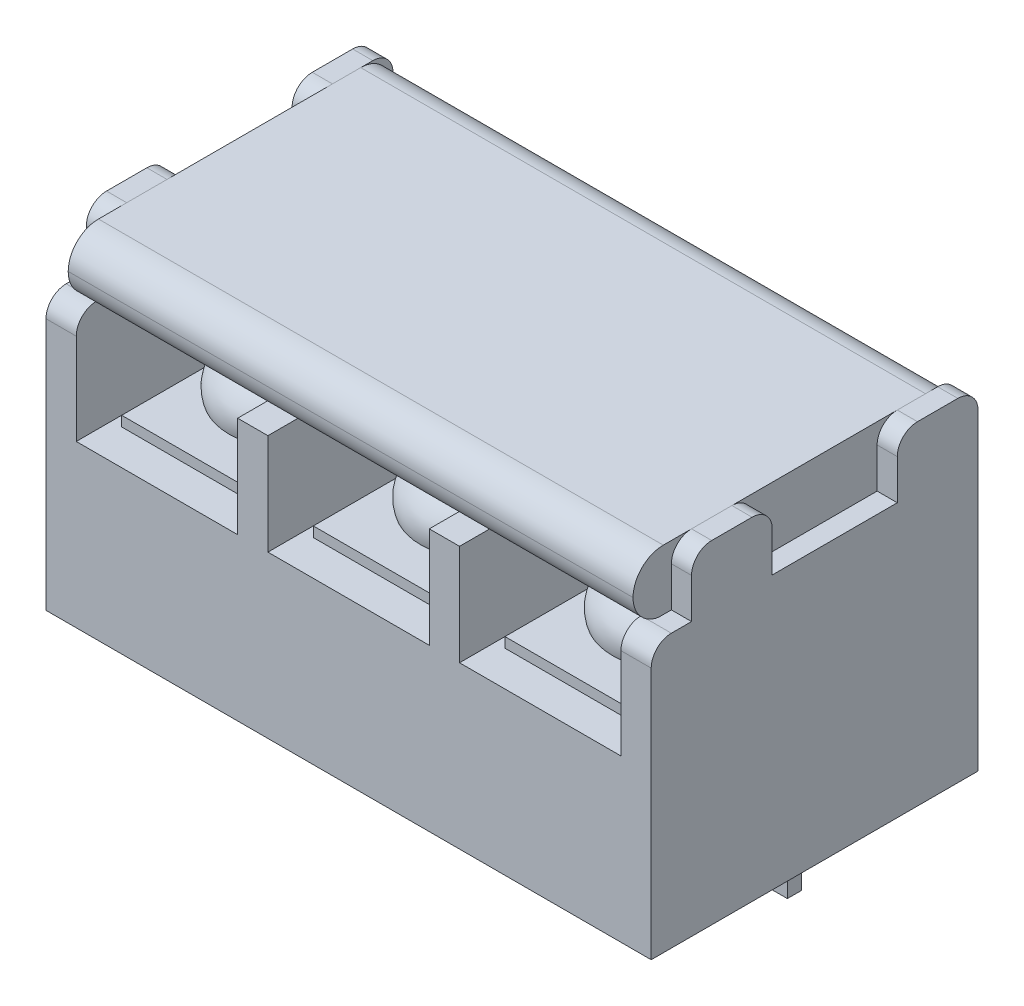
SolidWorks part; units mm, degrees
ref_plane "前视基准面" through (0, 0, 0) normal (0, 0, 1) x (1, 0, 0)
ref_plane "上视基准面" through (0, 0, 0) normal (0, 1, 0) x (1, 0, 0)
ref_plane "右视基准面" through (0, 0, 0) normal (1, 0, 0) x (0, 0, -1)
sketch "草图1" plane through (0, 0, 0) normal (0, 1, 0) x (1, 0, 0)
  line L1 (-15, -8.1) -> (15, -8.1)
  line L2 (-15, -8.1) -> (-15, 8.1)
  line L3 (-15, 8.1) -> (15, 8.1)
  line L4 (15, -8.1) -> (15, 8.1)
  line L5 (-15, -8.1) -> (15, 8.1) construction
  line L6 (-15, 8.1) -> (15, -8.1) construction
  point P0 (0, 0)
  dimension "D1" = 16.2
  dimension "D2" = 30
extrude "凸台-拉伸1" add sketch "草图1" along normal blind 16.5
sketch "草图2" plane through (0, 0, 8.1) normal (0, 0, 1) x (1, 0, 0)
  line L0 (-15, 16.5) -> (15, 16.5) construction
  line L1 (-13.5, 16.5) -> (-5.5, 16.5)
  line L2 (-13.5, 16.5) -> (-13.5, 8)
  line L3 (-13.5, 8) -> (-5.5, 8)
  line L4 (-5.5, 16.5) -> (-5.5, 8)
  line L5 (-15, 16.5) -> (-15, 0) construction
  line L6 (-4, 16.5) -> (4, 16.5)
  line L7 (-4, 16.5) -> (-4, 8)
  line L8 (-4, 8) -> (4, 8)
  line L9 (4, 16.5) -> (4, 8)
  line L10 (5.5, 16.5) -> (13.5, 16.5)
  line L11 (5.5, 16.5) -> (5.5, 8)
  line L12 (5.5, 8) -> (13.5, 8)
  line L13 (13.5, 16.5) -> (13.5, 8)
  line L14 (15, 16.5) -> (15, 0) construction
  dimension "D1" = 1.5
  dimension "D2" = 1.5
  dimension "D3" = 1.5
  dimension "D4" = 1.5
  dimension "D5" = 8.5
extrude "切除-拉伸1" cut sketch "草图2" against normal blind 13.5
sketch "草图3" plane through (0, 0, -8.1) normal (0, 0, -1) x (-1, 0, 0)
  line L0 (-13.5, 8) -> (-13.5, 16.5) construction
  line L1 (-13.5, 11.5) -> (-5.5, 11.5)
  line L2 (-13.5, 11.5) -> (-13.5, 0)
  line L3 (-13.5, 0) -> (-5.5, 0)
  line L4 (-5.5, 11.5) -> (-5.5, 0)
  line L5 (-15, 0) -> (15, 0) construction
  line L6 (-4, 8) -> (-4, 16.5) construction
  line L7 (-4, 11.5) -> (4, 11.5)
  line L8 (-4, 11.5) -> (-4, 0)
  line L9 (-4, 0) -> (4, 0)
  line L10 (4, 11.5) -> (4, 0)
  line L11 (5.5, 8) -> (5.5, 16.5) construction
  line L12 (5.5, 11.5) -> (13.5, 11.5)
  line L13 (5.5, 11.5) -> (5.5, 0)
  line L14 (5.5, 0) -> (13.5, 0)
  line L15 (13.5, 11.5) -> (13.5, 0)
  line L16 (-5.5, 16.5) -> (-5.5, 8) construction
  line L17 (4, 16.5) -> (4, 8) construction
  line L18 (13.5, 16.5) -> (13.5, 8) construction
  line L19 (-15, 16.5) -> (15, 16.5) construction
  point P22 (4, 5.75)
  dimension "D1" = 5
extrude "切除-拉伸2" cut sketch "草图3" against normal blind 1
sketch "草图4" plane through (0, 0, -5.4) normal (0, 0, 1) x (1, 0, 0)
  line L2 (13.5, 16.5) -> (-13.5, 16.5)
  line L3 (13.5, 16.5) -> (13.5, 13)
  line L4 (13.5, 13) -> (-13.5, 13)
  line L6 (-13.5, 16.5) -> (-13.5, 13)
  line L7 (-13.5, 16.5) -> (-13.5, 8) construction
  dimension "D1" = 3.5
extrude "切除-拉伸3" cut sketch "草图4" against normal through all both and the other way through all
sketch "草图5" plane through (-15, 0, 0) normal (-1, 0, 0) x (0, 0, 1)
  line L0 (-8.1, 16.5) -> (8.1, 16.5) construction
  line L1 (-4.1, 16.5) -> (2.1, 16.5)
  line L2 (-4.1, 16.5) -> (-4.1, 13.5196)
  line L3 (-4.1, 13.5196) -> (2.1, 13.5196)
  line L4 (2.1, 16.5) -> (2.1, 13.5196)
  line L5 (8.1, 16.5) -> (8.1, 0) construction
  line L6 (6.1, 16.5) -> (8.1, 16.5)
  line L7 (6.1, 16.5) -> (6.1, 13.5196)
  line L8 (6.1, 13.5196) -> (8.1, 13.5196)
  line L9 (8.1, 16.5) -> (8.1, 13.5196)
  line L10 (-8.1, 16.5) -> (-8.1, 0) construction
  dimension "D1" = 4
  dimension "D2" = 4
  dimension "D3" = 2
extrude "切除-拉伸4" cut sketch "草图5" against normal through all
sketch "草图12" plane through (0, 0, 8.1) normal (0, 0, 1) x (1, 0, 0)
  line L0 (-13.5, 13.5196) -> (-15, 13.5196) construction
  line L1 (-14, 16.5) -> (14, 16.5)
  line L2 (-14, 16.5) -> (-14, 13.5196)
  line L3 (-14, 13.5196) -> (14, 13.5196)
  line L4 (14, 16.5) -> (14, 13.5196)
  line L5 (-13.5, 16.5) -> (-15, 16.5) construction
  line L6 (0, 0) -> (0, 19.6469) construction
  dimension "D1" = 28
extrude "切除-拉伸6" cut sketch "草图12" against normal through all
sketch "草图10" plane through (0, 0, 0) normal (1, 0, 0) x (0, 0, -1)
  line L1 (8, 13.5) -> (-8, 13.5)
  line L2 (8, 13.5) -> (8, 16.5)
  line L3 (8, 16.5) -> (-8, 16.5)
  line L4 (-8, 13.5) -> (-8, 16.5)
  line L5 (4.1, 16.5) -> (8.1, 16.5) construction
  dimension "D1" = 3
  dimension "D2" = 16
extrude "凸台-拉伸3" add sketch "草图10" along normal mid plane 28 separate body
fillet "圆角2" radius 1 2 edges at (-14.25, 13.5196, 8.1) (14.25, 13.5196, 8.1)
fillet "圆角1" radius 1.5 4 edges at (0, 13.5, -8) (0, 16.5, -8) (0, 13.5, 8) (0, 16.5, 8)
sketch "草图6" plane through (0, 8, 0) normal (0, 1, 0) x (1, 0, 0)
  line L0 (-9.5, 8.9662) -> (-9.5, -8.9812) construction
  line L1 (-13, 3.65) -> (-6, 3.65)
  line L2 (-13, 3.65) -> (-13, -6.35)
  line L3 (-13, -6.35) -> (-6, -6.35)
  line L4 (-6, 3.65) -> (-6, -6.35)
  line L5 (-13.5, 5.4) -> (-13.5, -8.1) construction
  line L6 (-5.5, 5.4) -> (-5.5, -8.1) construction
  line L7 (-11.9553, -1.35) -> (-7.0447, -1.35) construction
  line L8 (-13.5, 5.4) -> (-5.5, 5.4) construction
  line L9 (-13.5, -8.1) -> (-5.5, -8.1) construction
  point P7 (-9.5, -0.0075)
  point P13 (-9.5, -1.35)
  dimension "D1" = 10
  dimension "D2" = 7
extrude "凸台-拉伸2" add sketch "草图6" along normal blind 0.5 separate body
ref_plane "基准面1" through (0, 0, 1.35) normal (0, 0, 1) x (1, 0, 0)
sketch "草图8" plane through (0, 0, 1.35) normal (0, 0, 1) x (1, 0, 0)
  line L0 (-9.5, 8.5) -> (-9.5, 13.5286) construction
  line L2 (-13, 8.5) -> (-6, 8.5) construction
  line L3 (-7.83, 10.55) -> (-9.5, 10.55)
  line L4 (-9.5, 10.55) -> (-9.5, 8.5)
  line L5 (-9.5, 8.5) -> (-6.349, 8.5)
  arc A0 (-7.83, 10.55) -> (-6.349, 8.5) centre (-7.83, 8.99) cw
  dimension "D1" = 1.67
  dimension "D3" = 1.56
  dimension "D2" = 2.05
revolve "旋转1" add sketch "草图8" angle 360 about L0
sketch "草图9" plane through (0, 10.55, 0) normal (0, 1, 0) x (1, 0, 0)
  line L0 (-6, -6.35) -> (-6, 3.65) construction
  line L1 (-13, -1.95) -> (-6, -1.95)
  line L2 (-13, -1.95) -> (-13, -0.75)
  line L3 (-13, -0.75) -> (-6, -0.75)
  line L4 (-6, -1.95) -> (-6, -0.75)
  line L5 (-13, -1.95) -> (-6, -0.75) construction
  line L6 (-13, -0.75) -> (-6, -1.95) construction
  line L8 (-10.1, -3.35) -> (-8.9, -3.35)
  line L9 (-10.1, -3.35) -> (-10.1, 0.65)
  line L10 (-10.1, 0.65) -> (-8.9, 0.65)
  line L11 (-8.9, -3.35) -> (-8.9, 0.65)
  line L12 (-10.1, -3.35) -> (-8.9, 0.65) construction
  line L13 (-10.1, 0.65) -> (-8.9, -3.35) construction
  point P0 (-9.5, -1.35)
  point P7 (-9.5, -1.35)
  circle M5 centre (-9.5, -1.35) radius 1.67
  dimension "D1" = 1.2
  dimension "D2" = 1.2
  dimension "D3" = 4
extrude "切除-拉伸5" cut sketch "草图9" against normal blind 1.5 contours L11 L10 L9 M5 | L3 L11 L9 M5 | L3 L4 L1 L2 | L11 L10 L9 L8 region at (-9.5, 10.55, 0.2328) region at (-9.5, 10.55, -0.4652)
sketch "草图11" plane through (0, 0, 0) normal (0, -1, 0) x (1, 0, 0)
  line L0 (-9.5, -7.1) -> (-9.5, -2.1411) construction
  line L1 (-10.25, -3.4) -> (-8.75, -3.4)
  line L2 (-10.25, -3.4) -> (-10.25, -4.1)
  line L3 (-10.25, -4.1) -> (-8.75, -4.1)
  line L4 (-8.75, -3.4) -> (-8.75, -4.1)
  line L5 (-5.5, -7.1) -> (-13.5, -7.1) construction
  line L6 (-13.5, -8.1) -> (-5.5, -8.1) construction
  point P10 (-9.5, -4.1)
  dimension "D1" = 1.5
  dimension "D2" = 0.7
  dimension "D3" = 4
extrude "凸台-拉伸4" add sketch "草图11" along normal blind 5.5
pattern_linear "阵列(线性)5" count 3 spacing 9.5 along (1, 0, 0) of "凸台-拉伸2", "旋转1", "切除-拉伸5", "凸台-拉伸4"
fillet "圆角3" radius 1 8 edges at (14.5, 16.5, -8.1) (14.5, 16.5, -4.1) (14.5, 16.5, 2.1) (14.5, 16.5, 6.1) (-14.5, 16.5, 6.1) (-14.5, 16.5, 2.1) (-14.5, 16.5, -4.1) (-14.5, 16.5, -8.1)
